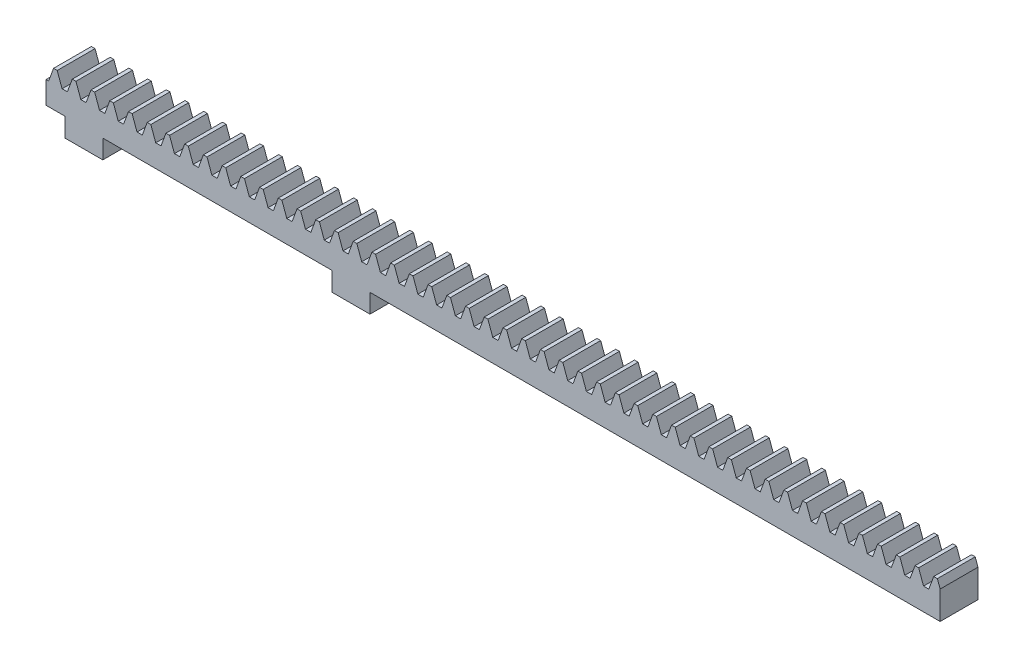
SolidWorks part; units mm, degrees
ref_plane "Plane1" through (0, 0, 0) normal (0, 0, 1) x (1, 0, 0)
ref_plane "Plane2" through (0, 0, 0) normal (0, 1, 0) x (1, 0, 0)
ref_plane "Plane3" through (0, 0, 0) normal (1, 0, 0) x (0, 0, -1)
sketch "HoldingSke" plane through (0, 0, 0) normal (0, 1, 0) x (1, 0, 0)
  line L0 (0, 0) -> (0.1392, 0.9903)
  line L1 (-15, 0) -> (100, 0) construction
  line L2 (0, 0) -> (-2.1039, 2.3779)
  line L3 (0, 0) -> (-11.863, 4.5341)
  line L4 (0, 0) -> (5.6657, 6.5177)
  line L5 (0, 0) -> (-23.7986, -8.8762)
  line L6 (0, 0) -> (-10.5278, -7.1032)
  line L9 (-71.009, 38.7566) -> (69.9449, 90.0596)
  line L10 (-76.2, 3.3779) -> (-71.2, 3.3779)
  line L11 (0, 0) -> (-6.35, 0)
  line L12 (-76.2, 101.6) -> (-76.162, 101.6)
  line L13 (24.9733, 27.94) -> (52.9518, 28.4284)
  line L14 (24.9733, 27.94) -> (24.9743, 27.94)
  line L15 (24.9733, 27.94) -> (100.4006, 29.5858)
  circle A0 centre (0, 0) radius 19.05
  circle A1 centre (0, 0) radius 2.5
  circle A2 centre (0, 0) radius 12.7
  dimension "MPH" = 5
  dimension "Diameter" = 38.1
  dimension "Num_teeth" = 49
  dimension "Pitch" = 1
  dimension "Width" = 6.35
  dimension "Show_teeth" = 998
  dimension "Thickness" = 12.7
  dimension "Ap" = 20
  dimension "Pitch_height" = 5
  dimension "Backlash" = 0.038
  dimension "Addendum_fac" = 1
  dimension "Dedendum_fac" = 1.25
  dimension "Clearance_fac" = 0.25
  dimension "Dedendum_add" = 0.001
  dimension "Length" = 150
  dimension "Module" = 1
sketch "BlankSke" plane through (0, 0, 0) normal (0, 0, 1) x (1, 0, 0)
  line L1 (0, 0) -> (150, 0)
  line L2 (0, 0) -> (0, 6)
  line L3 (0, 6) -> (150, 6)
  line L4 (150, 0) -> (150, 6)
  dimension "Length" = 150
  dimension "Blank_height" = 6
extrude "Blank" add sketch "BlankSke" against normal blind 6.35
sketch "TooCutSkeIll" plane through (0, 0, 0) normal (0, 0, 1) x (1, 0, 0)
  line L0 (-1.2538, 5.9737) -> (-0.5045, 3.9152)
  line L1 (-0.2687, 3.75) -> (0.2687, 3.75)
  line L2 (0.5045, 3.9152) -> (1.2538, 5.9737)
  line L3 (150, 6) -> (0, 6) construction
  line L4 (0, 0) -> (0, 64.897) construction
  line L5 (-13.208, 5) -> (12.954, 5) construction
  line L6 (0, 0) -> (150, 0) construction
  line L7 (0.8994, 5) -> (0.8994, 48.7463) construction
  line L8 (-0.8994, 5) -> (-0.8994, 48.7463) construction
  line L9 (1.2914, 6) -> (1.2914, 6.0254)
  line L10 (-1.2914, 6) -> (-1.2914, 6.0254)
  line L11 (-1.2914, 6.0254) -> (1.2914, 6.0254)
  arc A0 (0.2687, 3.75) -> (0.5045, 3.9152) centre (0.2687, 4.001) ccw
  arc A1 (-0.5045, 3.9152) -> (-0.2687, 3.75) centre (-0.2687, 4.001) ccw
  arc A2 (1.2914, 6) -> (1.2538, 5.9737) centre (1.2914, 5.96) ccw
  arc A3 (-1.2538, 5.9737) -> (-1.2914, 6) centre (-1.2914, 5.96) ccw
  dimension "Root_fillet" = 0.251
  dimension "Break_rad" = 0.04
  dimension "Pitch_height" = 5
  dimension "Gap_width" = 1.7988
  dimension "Dedendum" = 1.25
  dimension "Addendum_plus" = 1.0254
  dimension "Pressure_angle" = 20
extrude "ToothCutIll" [suppressed] cut sketch "TooCutSkeIll" against normal through all
sketch "TooCutSkeSim" plane through (0, 0, 0) normal (0, 0, 1) x (1, 0, 0)
  line L0 (0.4444, 3.75) -> (-0.4444, 3.75)
  line L1 (1.2726, 6.0254) -> (0.4444, 3.75)
  line L2 (0, 17.4625) -> (0, 53.467) construction
  line L3 (1.2726, 6.0254) -> (-1.2726, 6.0254)
  line L6 (-1.2726, 6.0254) -> (-0.4444, 3.75)
  line L9 (-0.8994, 5) -> (0.8994, 5) construction
  line L10 (0, 0) -> (150, 0) construction
  line L11 (0.8994, 5) -> (0.8994, 53.467) construction
  line L12 (-0.8994, 5) -> (-0.8994, 53.467) construction
  dimension "Pitch_height" = 5
  dimension "Pressure_angle" = 20
  dimension "Gap_width" = 1.7988
  dimension "Dedendum" = 1.25
  dimension "Addendum_plus" = 1.0254
extrude "ToothCutSim" cut sketch "TooCutSkeSim" against normal through all
pattern_linear "TeethCuts" count 49 spacing 3.1416 along (1, 0, 0) of "ToothCutIll", "ToothCutSim"
sketch "Sketch1" plane through (0, 0, 0) normal (0, -1, 0) x (1, 0, 0)
  line L0 (48, 0) -> (48, -6.35)
  line L1 (48, 0) -> (54.35, 0)
  line L2 (48, -6.35) -> (54.35, -6.35)
  line L3 (54.35, 0) -> (54.35, -6.35)
  line L6 (0, -6.35) -> (0, 0) construction
  line L7 (0, 0) -> (150, 0) construction
  line L8 (0, -6.35) -> (150, -6.35) construction
  line L9 (3.175, 0) -> (3.175, -6.35)
  line L10 (3.175, 0) -> (9.525, 0)
  line L11 (3.175, -6.35) -> (9.525, -6.35)
  line L12 (9.525, 0) -> (9.525, -6.35)
  dimension "D1" = 48
  dimension "D2" = 6.35
  dimension "D3" = 3.175
  dimension "D4" = 6.35
extrude "ElasticPegs_Extrude" add sketch "Sketch1" along normal blind 3.175
equation "' \"Module@HoldingSke\" = 6.35"
equation "' \"Num_teeth@HoldingSke\" = 12"
equation "' \"Ap@HoldingSke\" =  20"
equation "' \"Width@HoldingSke\" = 0.25 * 25.4"
equation "' \"Show_teeth@HoldingSke\" = 500"
equation "' \"Backlash@HoldingSke\" = 0.009 * 25.4"
equation "' \"Addendum_fac@HoldingSke\" = 1.0"
equation "' \"Dedendum_fac@HoldingSke\" = 1.25"
equation "' \"Dedendum_add@HoldingSke\" = 0.00005 * 25.4"
equation "' \"Clearance_fac@HoldingSke\" = 0.25"
equation "' \"Pitch_height@HoldingSke\" = 1 * 25.4"
equation "' \"Length@HoldingSke\" = 4.71 * 25.4"
equation "\"Pitch@HoldingSke\" = 1 / \"Module@HoldingSke\""
equation "\"MPH@HoldingSke\" = \"Dedendum_fac@HoldingSke\" / \"Pitch@HoldingSke\" + 2 * \"Dedendum_add@HoldingSke\" + 0.002 * 25.4"
equation "\"MPH@HoldingSke\" = ((sgn( \"MPH@HoldingSke\" - \"Pitch_height@HoldingSke\")+1)*( \"MPH@HoldingSke\" - \"Pitch_height@HoldingSke\"))/2 + \"Pitch_height@HoldingSke\""
equation "\"Blank_height@BlankSke\" = \"Pitch_height@HoldingSke\" + \"Addendum_fac@HoldingSke\"  / \"Pitch@HoldingSke\" "
equation "\"Length@BlankSke\" =  \"Length@HoldingSke\""
equation "\"Face_width@Blank\" = \"Width@HoldingSke\""
equation "\"Pressure_angle@TooCutSkeIll\" = \"Ap@HoldingSke\""
equation "\"Addendum_plus@TooCutSkeIll\" =  \"Addendum_fac@HoldingSke\"  / \"Pitch@HoldingSke\" + 0.001 *25.4"
equation "\"Dedendum@TooCutSkeIll\" = \"Dedendum_fac@HoldingSke\"  / \"Pitch@HoldingSke\""
equation "\"Pitch_height@TooCutSkeIll\" =  \"MPH@HoldingSke\""
equation "\"Gap_width@TooCutSkeIll\" = 3.14159265 / 2 / \"Pitch@HoldingSke\" + 6 * \"Backlash@HoldingSke\""
equation "\"Pressure_angle@TooCutSkeSim\" = \"Ap@HoldingSke\""
equation "\"Addendum_plus@TooCutSkeSim\" =  \"Addendum_fac@HoldingSke\"  / \"Pitch@HoldingSke\" + 0.001 * 25.4"
equation "\"Dedendum@TooCutSkeSim\" = \"Dedendum_fac@HoldingSke\"  / \"Pitch@HoldingSke\""
equation "\"Pitch_height@TooCutSkeSim\" =  \"MPH@HoldingSke\""
equation "\"Gap_width@TooCutSkeSim\" = 3.14159265 / 2 / \"Pitch@HoldingSke\" + 6 * \"Backlash@HoldingSke\""
equation "\"Root_fillet@TooCutSkeIll\" = \"Clearance_fac@HoldingSke\" / \"Pitch@HoldingSke\" + \"Dedendum_add@HoldingSke\""
equation "\"Break_rad@TooCutSkeIll\" = 0.02 / \"Pitch@HoldingSke\" * 2"
equation "\"Linear_pitch@TeethCuts\" = 3.14159265 / \"Pitch@HoldingSke\""
equation "\"Num_teeth@HoldingSke\" = int( ( \"Length@HoldingSke\" + 0 ) / (3.14159265 / \"Pitch@HoldingSke\")) + 0.9999  + 1"
equation " \"Num_teeth@TeethCuts\" = int( \"Show_teeth@HoldingSke\" ) + 1"
equation " \"Num_teeth@TeethCuts\" = ((sgn( \"Num_teeth@TeethCuts\" - \"Num_teeth@HoldingSke\" )-1)*( \"Num_teeth@TeethCuts\" - \"Num_teeth@HoldingSke\" ))/-2+ \"Num_teeth@HoldingSke\""
equation " \"Num_teeth@TeethCuts\" = ((sgn( \"Num_teeth@TeethCuts\" - 2.0)+1)*( \"Num_teeth@TeethCuts\" - 2.0))/2 +2.0"
equation "\"CageLeftBottomEdge\"=22.11mm"
equation "\"CageLeftTopEdge\"=22.11mm"
equation "\"CageRightBottomEdge\"=21.63mm"
equation "\"CageRightTopEdge\"=21.63mm"
equation "\"CageHeight\"=86.04mm"
equation "\"CageLength\"=73.76mm"
equation "\"CageTopScrewClearance\"=10mm"
equation "\"CageBottomScrewClearance\"=25mm"
equation "\"CageLeftTopDepth\"= 11.65mm"
equation "\"CageLeftBottomDepth\"=11.11mm"
equation "\"CageLeftTopHeight\"=8.56175mm"
equation "\"CageLeftBottomHeight\"=16mm"
equation "\"CageRightTopDepth\"= 11.05mm"
equation "\"CageRightBottomDepth\"=10.58mm"
equation "\"CageRightTopHeight\"=9.6mm"
equation "\"CageRightBottomHeight\"=15.49mm"
equation "\"CageLeftTopChannelDepth\"=2.41908mm"
equation "\"CageLeftBottomChannelDepth\"=2.588mm"
equation "\"CageLeftChannelHeight\"=11.7mm"
equation "\"CageRightTopChannelDepth\"=2.32mm"
equation "\"CageRightBottomChannelDepth\"=2.318mm"
equation "\"CageRightChannelHeight\"=10mm"
equation "\"CageChanRelHeight\"=23.99mm"
equation "\"CageChanRelDepth\"=5.492mm"
equation "\"CageChamberRadius\"=16.261mm"
equation "\"CageScrewDiameter\"=4.8mm"
equation "\"CageSetScrewDiameter\"=3.5mm"
equation "\"CageAxleRadius\"=6.639mm"
equation "\"CageAxleKeyHeight\"=1.619mm"
equation "\"CageAxleKeyWidth\"=2.662mm"
equation "\"CageHoseWindowWidth\"=16.29mm"
equation "\"CageHoseWindowHeight\"=26.5mm"
equation "\"CageHoseWindow-Edge\"=8.89mm"
equation "\"CageScrew-VerticalEdge\"=5.0mm"
equation "\"CageScrew-HorizontalEdge\"=7.5mm"
equation "\"CageScrew-HoseCornerScrewEdge\"=4.45mm"
equation "\"CageAxle-BottomEdge\"=56.05mm"
equation "\"CageAxle-FrontEdge\"=46.03mm"
equation "\"CageBackSetScrew-Axle\"=40mm"
equation "\"CageFrontSetScrew-Axle\"=22mm"
equation "\"CageVelocityWindow-BackEdge\"=34.8mm"
equation "\"CageVelocityWindow-BottomEdge\"=27.55mm"
equation "\"CageVelocityWindowHeight\"=22.29mm"
equation "\"CageVelocityWindowWidth\"=12.61mm"
equation "\"TriggerSlot-BottomEdge\"=6.35mm"
equation "\"TriggerSlot-FrontEdge\"=15mm"
equation "\"TriggerSlotSize\"=6.7mm"
equation "\"TriggerRackOffset\"=.236224in"
equation "\"TriggerSlotSizeInt\"=.25in"
equation "\"MotorMountLegLength\"=.25in"
equation "\"GearOffset\"=.264907in"
equation "\"TriggerSlotSpacing\"=.25in"
equation "\"TriggerMiniSlotWidth\"=3.5mm"
equation "\"TriggerRackWidth\"=6.5mm"
equation "\"TGMGearFaceDiameter\"=24.40mm"
equation "\"TGMCylinderLength\"=15.00mm"
equation "\"TGMScrewHole-Center\"=8.70mm"
equation "\"TGMScrewHoleDiameter\"=5.04mm"
equation "\"TGMCenterHoleDiameter\"=9.50mm"
equation "\"TGMShaftCollarSideLength\"=19.00mm"
equation "\"TGMShaftCollarDockingDepth\"=7.00mm"
equation "\"whitemotordepth\"=11.27mm"
equation "\"whitemotorbackdepth\"=3.845mm"
equation "\"whitemotoraxledepth\" = 3.5mm"
equation "\"whitemotoraxleoffset\"=11.4mm"
equation "\"whitemotorwidth\"=12.07mm"
equation "\"whitemotorheight\"=16.68mm"
equation "\"whitemotorcylinderlength\" =13.04mm"
equation "\"whitemotorcylinderradius\"=3.845mm"
equation "\"whitemotorcylinderoffset\"=2.35mm"
equation "\"whitemotorcutoutlength\"=1.88mm"
equation "\"whitemotorouterrad\"=5mm"
equation "\"whitemotorinnerrad\"=2.95mm"
equation "\"elasticracklength\"=2in"
equation "\"elasticrackpegsize\"=.25in"
equation "\"elasticrackpegbuffer\"=.125in"
equation "\"elasticrackpegspacing\"=1.76476378in"
equation "\"elasticbaybuffer\"=.25in"
equation "\"elasticdepth\"=.125in"
equation "\"elasticbaydepth\"=.75in"
equation "\"motormountwidth\"=12mm"
equation "\"motormountcornerfillet\"=3mm"
equation "\"D2@Sketch1\"=\"elasticrackpegsize\""
equation "\"D4@Sketch1\"=\"elasticrackpegsize\""
equation "\"D3@Sketch1\"=\"elasticrackpegsize\"/2"
equation "\"D1@Sketch1\"=\"elasticrackpegspacing\"+\"elasticrackpegsize\"/2"
